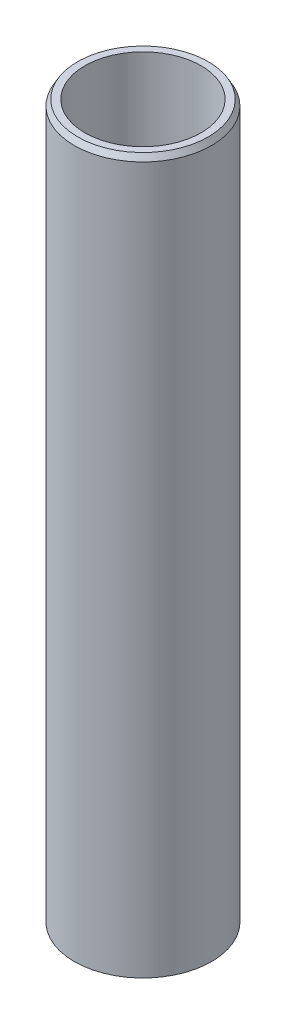
SolidWorks part; units mm, degrees
ref_plane "Front Plane" through (0, 0, 0) normal (0, 0, 1) x (1, 0, 0)
ref_plane "Top Plane" through (0, 0, 0) normal (0, 1, 0) x (1, 0, 0)
ref_plane "Right Plane" through (0, 0, 0) normal (1, 0, 0) x (0, 0, -1)
sketch "Sketch1" plane through (0, 0, 0) normal (0, 1, 0) x (1, 0, 0)
  circle A0 centre (0, 0) radius 57.5
  dimension "SHAFT_OD" = 115
extrude "Boss-Extrude1" add sketch "Sketch1" along normal blind 600
sketch "Sketch2" plane through (0, 0, 0) normal (0, 1, 0) x (1, 0, 0)
  circle A0 centre (0, 0) radius 48.7226
  dimension "BORE_D" = 97.4452
extrude "Cut-Extrude1" cut sketch "Sketch2" along normal through all
chamfer "Chamfer1" distance 4.8669 angle 30 2 edges at (0, 600, 57.5) (0, 0, 57.5) first distance on face at (0, 600, 57.5) first distance on face at (0, 0, 48.7226)
